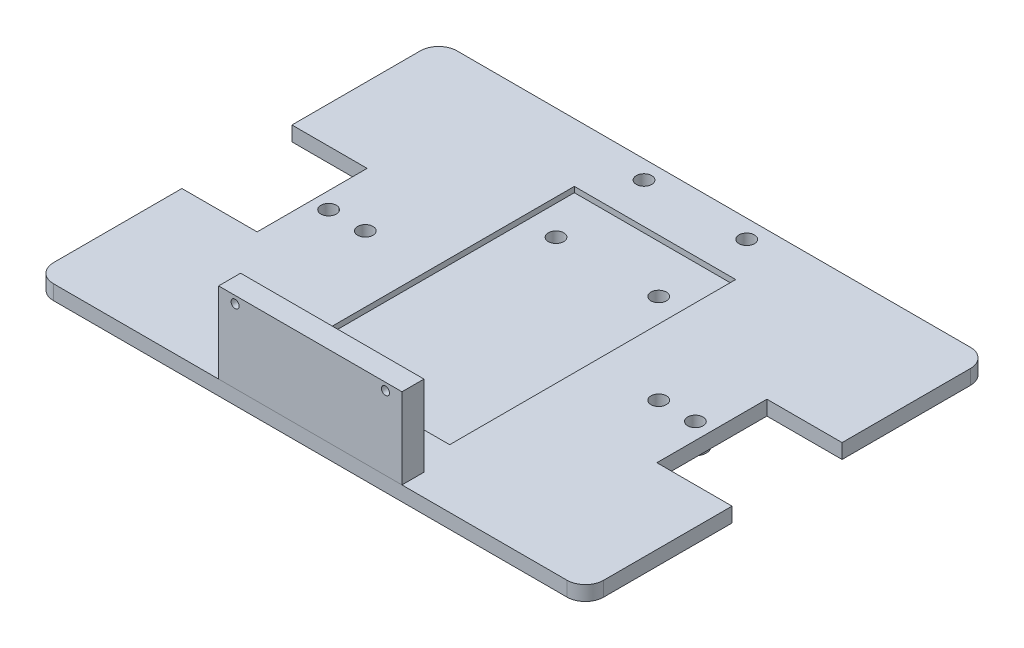
SolidWorks part; units mm, degrees
ref_plane "Front Plane" through (0, 0, 0) normal (0, 0, 1) x (1, 0, 0)
ref_plane "Top Plane" through (0, 0, 0) normal (0, 1, 0) x (1, 0, 0)
ref_plane "Right Plane" through (0, 0, 0) normal (1, 0, 0) x (0, 0, -1)
sketch "Sketch1" plane through (0, 0, 0) normal (0, 1, 0) x (1, 0, 0)
  line L0 (-75, 0) -> (75, 0) construction
  line L1 (-75, -55) -> (75, -55)
  line L2 (-75, -55) -> (-75, 55)
  line L3 (-75, 55) -> (75, 55)
  line L4 (75, -55) -> (75, 55)
  line L5 (-75, -55) -> (75, 55) construction
  line L6 (-75, 55) -> (75, -55) construction
  point P0 (0, 0)
  dimension "D1" = 150
  dimension "D2" = 110
extrude "Boss-Extrude1" add sketch "Sketch1" along normal blind 4
fillet "Fillet1" radius 5 4 edges at (-75, 2, -55) (-75, 2, 55) (75, 2, -55) (75, 2, 55)
sketch "Sketch2" plane through (0, 4, 0) normal (0, 1, 0) x (1, 0, 0)
  line L0 (-75, 0) -> (75, 0) construction
  line L1 (-75, 50) -> (-75, -50) construction
  line L2 (75, -50) -> (75, 50) construction
  line L3 (0, 55) -> (0, -55) construction
  line L4 (70, 55) -> (-70, 55) construction
  line L5 (-70, -55) -> (70, -55) construction
  circle A0 centre (-50, 0) radius 2.1
  circle A1 centre (-40, 0) radius 2.1
  dimension "D1" = 4.2
  dimension "D2" = 50
  dimension "D3" = 4.2
  dimension "D4" = 40
extrude "Cut-Extrude1" cut sketch "Sketch2" against normal through all
sketch "Sketch3" plane through (0, 0, 0) normal (0, -1, 0) x (1, 0, 0)
  line L0 (-75, 0) -> (75, 0) construction
  line L1 (-75, -50) -> (-75, 50) construction
  line L2 (75, 50) -> (75, -50) construction
  line L3 (0, 55) -> (0, -55) construction
  line L4 (-70, 55) -> (70, 55) construction
  line L5 (70, -55) -> (-70, -55) construction
  circle A0 centre (-50, 0) radius 3
  circle A1 centre (-40, 0) radius 3
  dimension "D1" = 6
  dimension "D2" = 6
extrude "Boss-Extrude2" add sketch "Sketch3" along normal blind 2
mirror "Mirror1" about plane through (0, 0, 0) normal (1, 0, 0) of "Boss-Extrude2", "Cut-Extrude1"
sketch "Sketch4" plane through (0, 4, 0) normal (0, 1, 0) x (1, 0, 0)
  line L0 (0, -55) -> (0, 55) construction
  line L1 (-22, -39) -> (-6, -39)
  line L2 (-22, -39) -> (-22, 39)
  line L3 (-22, 39) -> (22, 39)
  line L4 (22, -39) -> (22, 39)
  line L5 (-22, -39) -> (22, 39) construction
  line L6 (-22, 39) -> (22, -39) construction
  line L7 (-70, -55) -> (70, -55) construction
  line L8 (70, 55) -> (-70, 55) construction
  line L9 (6, -39) -> (22, -39)
  line L10 (-6, -43) -> (6, -43)
  line L11 (-6, -43) -> (-6, -39)
  line L13 (6, -43) -> (6, -39)
  line L14 (-6, -43) -> (6, -39) construction
  line L15 (-6, -39) -> (6, -43) construction
  point P0 (0, 0)
  point P15 (0, -41)
  dimension "D1" = 44
  dimension "D2" = 78
  dimension "D3" = 0
  dimension "D4" = 4
  dimension "D5" = 12
extrude "Cut-Extrude2" cut sketch "Sketch4" against normal blind 1.5
sketch "Sketch7" plane through (0, 0, 55) normal (0, 0, 1) x (1, 0, 0)
  line L0 (-70, 4) -> (70, 4) construction
  line L1 (-25, 4) -> (25, 4)
  line L2 (-25, 4) -> (-25, 26)
  line L3 (-25, 26) -> (25, 26)
  line L4 (25, 4) -> (25, 26)
  line L5 (-25, 4) -> (25, 26) construction
  line L6 (-25, 26) -> (25, 4) construction
  line L7 (70, 0) -> (70, 4) construction
  point P0 (0, 4)
  point P10 (0, 26)
  dimension "D1" = 50
  dimension "D2" = 22
  dimension "D3" = 45
extrude "Boss-Extrude4" add sketch "Sketch7" against normal blind 6 separate body
sketch "Sketch8" plane through (0, 0, 49) normal (0, 0, -1) x (-1, 0, 0)
  line L0 (0, 4) -> (0, 26) construction
  line L1 (25, 4) -> (-25, 4) construction
  line L2 (-25, 26) -> (25, 26) construction
  circle A0 centre (-20.5, 24) radius 1.1
  circle A1 centre (20.5, 24) radius 1.1
  dimension "D1" = 2.2
  dimension "D2" = 20.5
  dimension "D3" = 20
extrude "Cut-Extrude3" cut sketch "Sketch8" against normal through all
sketch "Sketch10" plane through (0, 4, 0) normal (0, 1, 0) x (1, 0, 0)
  circle A0 centre (-50, 0) radius 2.1
  circle A1 centre (-40, 0) radius 2.1
  circle A2 centre (40, 0) radius 2.1
  circle A3 centre (50, 0) radius 2.1
  dimension "D1" = 4.2
  dimension "D2" = 4.2
  dimension "D3" = 4.2
  dimension "D4" = 4.2
extrude "Cut-Extrude5" cut sketch "Sketch10" against normal through all
sketch "Sketch11" plane through (0, 4, 0) normal (0, 1, 0) x (1, 0, 0)
  line L0 (75, -50) -> (75, 50) construction
  line L1 (54.5, -15) -> (75, -15)
  line L2 (54.5, -15) -> (54.5, 15)
  line L3 (54.5, 15) -> (75, 15)
  line L4 (75, -15) -> (75, 15)
  line L5 (54.5, -15) -> (75, 15) construction
  line L6 (54.5, 15) -> (75, -15) construction
  line L7 (0, -15.4) -> (0, 15.4) construction
  line L8 (-54.5, 15) -> (-75, -15) construction
  line L9 (-54.5, -15) -> (-75, 15) construction
  line L10 (-75, -15) -> (-75, 15)
  line L11 (-54.5, 15) -> (-75, 15)
  line L12 (-54.5, -15) -> (-54.5, 15)
  line L13 (-54.5, -15) -> (-75, -15)
  point P0 (64.75, 0)
  point P14 (-64.75, 0)
  dimension "D1" = 54.5
  dimension "D2" = 15
  dimension "D3" = 15
extrude "Cut-Extrude6" cut sketch "Sketch11" against normal through all
sketch "Sketch12" plane through (0, 0, 0) normal (0, -1, 0) x (1, 0, 0)
  line L0 (70, -55) -> (-70, -55) construction
  line L1 (-14, -50) -> (14, -50) construction
  line L2 (-14, -50) -> (-14, -26) construction
  line L3 (-14, -26) -> (14, -26) construction
  line L4 (14, -50) -> (14, -26) construction
  line L5 (-14, -50) -> (14, -26) construction
  line L6 (-14, -26) -> (14, -50) construction
  circle A0 centre (-14, -26) radius 4
  circle A1 centre (14, -26) radius 4
  circle A2 centre (14, -50) radius 4
  circle A3 centre (-14, -50) radius 4
  point P0 (0, -38)
  dimension "D4" = 8
  dimension "D1" = 28
  dimension "D2" = 24
  dimension "D3" = 5
extrude "Boss-Extrude5" add sketch "Sketch12" along normal blind 3.5
sketch "Sketch13" plane through (0, 4, 0) normal (0, 1, 0) x (1, 0, 0)
  circle A0 centre (14, 26) radius 2.1
  circle A4 centre (-14, 50) radius 2.1
  circle A6 centre (14, 50) radius 2.1
  circle A7 centre (-14, 26) radius 2.1
  dimension "D1" = 4.2
  dimension "D2" = 4.2
  dimension "D3" = 4.2
  dimension "D4" = 4.2
extrude "Cut-Extrude7" cut sketch "Sketch13" against normal through all
